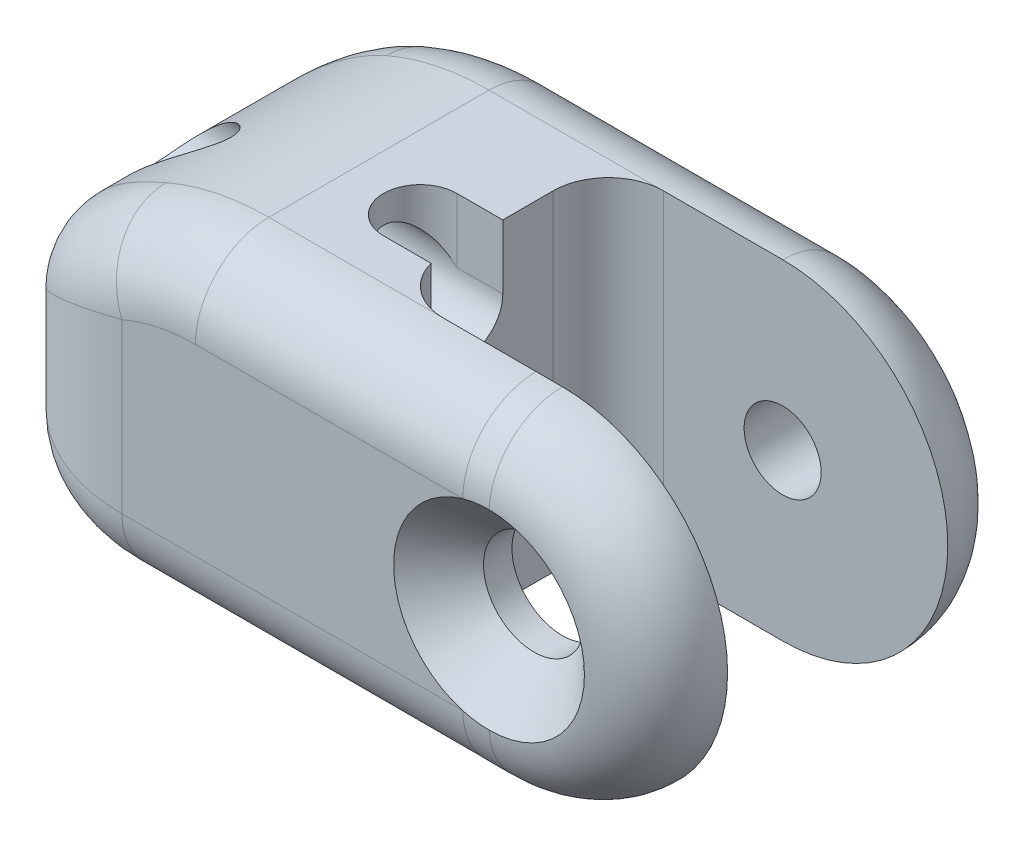
SolidWorks part; units mm, degrees
ref_plane "Front Plane" through (0, 0, 0) normal (0, 0, 1) x (1, 0, 0)
ref_plane "Top Plane" through (0, 0, 0) normal (0, 1, 0) x (1, 0, 0)
ref_plane "Right Plane" through (0, 0, 0) normal (1, 0, 0) x (0, 0, -1)
sketch "Sketch2" plane through (0, 0, 0) normal (0, 1, 0) x (1, 0, 0)
  line L0 (-5.5, 10) -> (23.5, 10)
  line L1 (23.5, 10) -> (23.5, 6)
  line L2 (23.5, 6) -> (8, 6)
  line L3 (5, 3) -> (5, -3)
  line L4 (8, -6) -> (23.5, -6)
  line L5 (23.5, -6) -> (23.5, -10)
  line L8 (-49.3622, 0) -> (56.3776, 0) construction
  line L9 (0, 21.2372) -> (0, -19.0689) construction
  line L10 (5, 3) -> (8, 3) construction
  line L11 (8, 3) -> (8, 6) construction
  line L16 (-5.5, -10) -> (23.5, -10)
  arc A0 (8, 6) -> (5, 3) centre (8, 3) ccw
  arc A1 (8, -6) -> (5, -3) centre (8, -3) cw
  arc A3 (-5.5, 10) -> (-5.5, -10) centre (-5.5, 0) ccw
  point P13 (8, 3)
  dimension "D2" = 20
  dimension "D3" = 4
  dimension "D4" = 18.5
  dimension "D5" = 12
  dimension "D6" = 3
  dimension "D7" = 3
  dimension "D8" = 5
  dimension "D9" = 29
extrude "Boss-Extrude1" add sketch "Sketch2" along normal blind 18
sketch "Sketch5" plane through (0, 0, 10) normal (0, 0, 1) x (1, 0, 0)
  line L0 (-13.5058, 9) -> (31.8434, 9) construction
  line L1 (-5.5, 18) -> (-5.5, 0) construction
  line L2 (23.5, 18) -> (23.5, 0) construction
  line L3 (-5.5, 18) -> (23.5, 18) construction
  line L4 (14.5, 18) -> (14.5, 0) construction
  line L5 (-15.5, 0) -> (-5.5, 0) construction
  line L7 (-15.5, 0) -> (-15.5, 4)
  line L8 (-15.5, 0) -> (14.5, 0)
  line L9 (-1.5, 18) -> (14.5, 18)
  arc A1 (14.5, 0) -> (14.5, 18) centre (14.5, 9) ccw
  arc A2 (-1.5, 18) -> (-15.5, 4) centre (-1.5, 4) ccw
  dimension "D2" = 4
  dimension "D1" = 9
  dimension "D3" = 10
extrude "Cut-Extrude1" cut sketch "Sketch5" against normal blind 20 flip side to cut
sketch "Sketch6" plane through (0, 0, 10) normal (0, 0, 1) x (1, 0, 0)
  line L0 (14.5, 0) -> (14.5, 18) construction
  point P4 (14.5, 9)
hole_wizard "CSK for M5 Countersunk Flat Head Screw1" positions "Sketch7" profile "Sketch8" countersink size "M5" standard "DIN" end condition up to next
sketch "Sketch7" plane through (0, 0, 10) normal (0, 0, 1) x (1, 0, 0)
  point P0 (14.5, 9)
sketch "Sketch8" plane through (14.5, 9, 10) normal (1, 0, 0) x (0, -1, 0)
  line L0 (0, 0) -> (0, 4)
  line L1 (0, 4) -> (2.75, 4)
  line L2 (2.75, 4) -> (2.75, 2.45)
  line L3 (2.75, 2.45) -> (5.2, 0)
  line L5 (5.2, 0) -> (0, 0)
  line L6 (-2.75, 2.45) -> (-5.2, 0) construction
  line L11 (0, -6.35) -> (0, 107.95) construction
  dimension "Thru Hole Dia." = 5.5
  dimension "Thru Hole Depth" = 4
  dimension "Near C'Sink Dia." = 10.4
  dimension "Near C'Sink Angle" = 90
hole_wizard "M5 Tapped Hole1" positions "Sketch9" profile "Sketch11" tap size "M5" standard "DIN" end condition through all
sketch "Sketch9" plane through (0, 0, 10) normal (0, 0, 1) x (1, 0, 0)
  point P0 (14.5, 9)
sketch "Sketch11" plane through (14.5, 9, 10) normal (1, 0, 0) x (0, -1, 0)
  line L0 (0, 0) -> (0, 20)
  line L1 (0, 20) -> (2.1, 20)
  line L2 (2.1, 20) -> (2.1, 3.1)
  line L3 (2.1, 3.1) -> (5.2, 0)
  line L5 (5.2, 0) -> (0, 0)
  line L6 (-2.1, 3.1) -> (-5.2, 0) construction
  line L11 (0, -6.35) -> (0, 107.95) construction
  dimension "Thru Tap Drill Dia." = 4.2
  dimension "Thru Tap Drill Depth" = 20
  dimension "Near C'Sink Dia." = 10.4
  dimension "Near C'Sink Angle" = 90
cosmetic thread "Hole Thread1" parameters "D2"=5
fillet "Fillet2" radius 4 10 edges at (-11.0658, 14.2223, -8.308) (-3.5212, 17.8533, -10) (6.5, 18, -10) (23.5, 9, -10) (-11.0658, 14.2223, 8.308) (-3.5212, 17.8533, 10) (6.5, 18, 10) (4.5, 0, 10) (-15.5, 0, 0) (4.5, 0, -10)
sketch "Sketch13" plane through (5, 0, 0) normal (1, 0, 0) x (0, 0, -1)
  line L0 (-1.75, -2.2721) -> (-1.75, 20.0856) construction
  line L1 (-3, 0) -> (3, 0) construction
  line L2 (-3, 18) -> (3, 18) construction
  circle A0 centre (-1.75, 14.5) radius 2
  point P4 (0, 0)
  dimension "D2" = 3.5
  dimension "D3" = 4
  dimension "D1" = 1.75
extrude "Cut-Extrude2" cut sketch "Sketch13" against normal through all both and the other way through all
sketch "Sketch14" plane through (0, 18, 0) normal (0, 1, 0) x (1, 0, 0)
  line L0 (5, 0) -> (-14.1432, 0) construction
  line L3 (5, -3) -> (5, 3) construction
  line L4 (2.5, -3.75) -> (7.4532, -3.75)
  line L5 (2.5, 0.25) -> (7.4532, 0.25)
  line L6 (7.4532, 0.25) -> (7.4532, -3.75)
  arc A0 (2.5, 0.25) -> (2.5, -3.75) centre (2.5, -1.75) ccw
  dimension "D1" = 1.75
  dimension "D2" = 2.5
extrude "Cut-Extrude3" cut sketch "Sketch14" against normal blind 3.5
